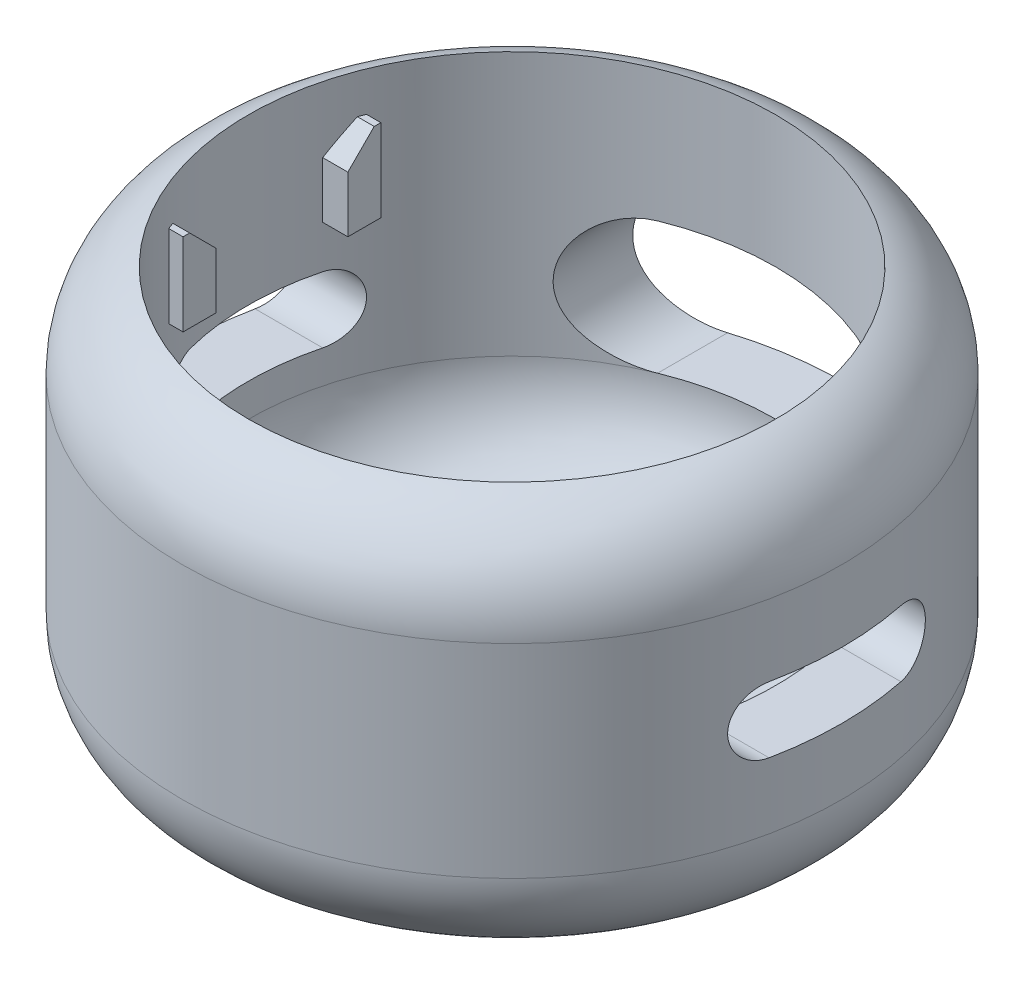
SolidWorks part; units mm, degrees
ref_plane "前视基准面" through (0, 0, 0) normal (0, 0, 1) x (1, 0, 0)
ref_plane "上视基准面" through (0, 0, 0) normal (0, 1, 0) x (1, 0, 0)
ref_plane "右视基准面" through (0, 0, 0) normal (1, 0, 0) x (0, 0, -1)
sketch "草图1" plane through (0, 0, 0) normal (0, 1, 0) x (1, 0, 0)
  circle A0 centre (3.8777, 2.7704) radius 7.5 construction
  circle A1 centre (3.8777, 2.7704) radius 10
  dimension "D1" = 15
  dimension "D2" = 20
extrude "凸台-拉伸1" add sketch "草图1" along normal blind 12
sketch "草图2" plane through (0, 0, 0) normal (0, 0, 1) x (1, 0, 0)
  line L0 (0.8777, 6) -> (6.8777, 6) construction
  line L1 (0.8777, 8) -> (6.8777, 8)
  line L2 (0.8777, 4) -> (6.8777, 4)
  line L3 (13.8777, 12) -> (-6.1223, 12) construction
  line L5 (-6.1223, 12) -> (-6.1223, 0) construction
  arc A0 (0.8777, 8) -> (0.8777, 4) centre (0.8777, 6) ccw
  arc A1 (6.8777, 4) -> (6.8777, 8) centre (6.8777, 6) ccw
  point P2 (3.8777, 6)
  dimension "D4" = 2
  dimension "D1" = 6
  dimension "D2" = 10
  dimension "D3" = 6
extrude "切除-拉伸1" cut sketch "草图2" against normal through all
sketch "草图3" plane through (0, 12, 0) normal (0, 1, 0) x (1, 0, 0)
  circle A1 centre (3.8777, 2.7704) radius 8
  dimension "D1" = 16
extrude "切除-拉伸2" cut sketch "草图3" against normal blind 11
fillet "圆角1" radius 3 3 edges at (3.8777, 12, 7.2296) (3.8777, 1, 5.2296) (3.8777, 0, 7.2296)
sketch "草图4" plane through (0, 0, 0) normal (1, 0, 0) x (0, 0, -1)
  line L0 (0.7704, 6) -> (4.7704, 6) construction
  line L1 (0.7704, 7) -> (4.7704, 7)
  line L2 (0.7704, 5) -> (4.7704, 5)
  line L4 (-7.2296, 9.1716) -> (-7.2296, 3) construction
  line L5 (-5.2296, 12) -> (10.7704, 12) construction
  arc A0 (0.7704, 7) -> (0.7704, 5) centre (0.7704, 6) ccw
  arc A1 (4.7704, 5) -> (4.7704, 7) centre (4.7704, 6) ccw
  point P2 (2.7704, 6)
  dimension "D2" = 1
  dimension "D1" = 10
  dimension "D3" = 4
  dimension "D4" = 6
extrude "切除-拉伸3" cut sketch "草图4" against normal through all and the other way through all
ref_plane "基准面1" through (0, 10.8, 0) normal (0, -1, 0) x (-1, 0, 0)
sketch "草图5" plane through (0, 10.8, 0) normal (0, -1, 0) x (-1, 0, 0)
  line L10 (-11.2939, 5.7704) -> (-13.4171, 5.7704) construction
  line L19 (-12.3555, 5.7704) -> (-10.8466, 5.7704)
  line L20 (-12.3555, 5.7704) -> (-12.3555, 4.7704)
  line L21 (-12.3555, 4.7704) -> (-10.8466, 4.7704)
  line L22 (-10.8466, 5.7704) -> (-10.8466, 4.7704)
  line L23 (-11.6237, 0.7704) -> (-13.6756, 0.7704) construction
  line L24 (-12.3555, 0.7704) -> (-10.8466, 0.7704)
  line L25 (-12.3555, 0.7704) -> (-12.3555, -0.2098)
  line L26 (-12.3555, -0.2098) -> (-10.8466, -0.2098)
  line L27 (-10.8466, 0.7704) -> (-10.8466, -0.2098)
  line L29 (4.8943, 5.7704) -> (3.1051, 5.7704)
  line L30 (4.8943, 5.7704) -> (4.8943, 4.7704)
  line L31 (4.8943, 4.7704) -> (3.1051, 4.7704)
  line L32 (3.1051, 5.7704) -> (3.1051, 4.7704)
  line L33 (5.9203, 0.7704) -> (3.8683, 0.7704) construction
  line L34 (4.8943, 0.7704) -> (3.1051, 0.7704)
  line L35 (4.8943, 0.7704) -> (4.8943, -0.2296)
  line L36 (4.8943, -0.2296) -> (3.1051, -0.2296)
  line L37 (3.1051, 0.7704) -> (3.1051, -0.2296)
  line L38 (3.5385, -0.2296) -> (5.6617, -0.2296) construction
  line L39 (5.9203, 4.7704) -> (3.8683, 4.7704) construction
  point P16 (4.8943, 4.7704)
  point P25 (0, 0)
  point P26 (-11.9994, 5.7704)
  point P27 (-12.3557, 5.7704)
  point P28 (0, 0)
  point P29 (0, 0)
  point P30 (0, 0)
  point P31 (0, 0)
  point P34 (0, 0)
extrude "凸台-拉伸3" add sketch "草图5" along normal blind 2.5
chamfer "倒角2" distance 0.8 angle 45 4 edges at (-3.4867, 10.8, -4.7704) (-3.4867, 10.8, -0.7704) (11.2351, 10.8, -0.7704) (11.2351, 10.8, -4.7704)
